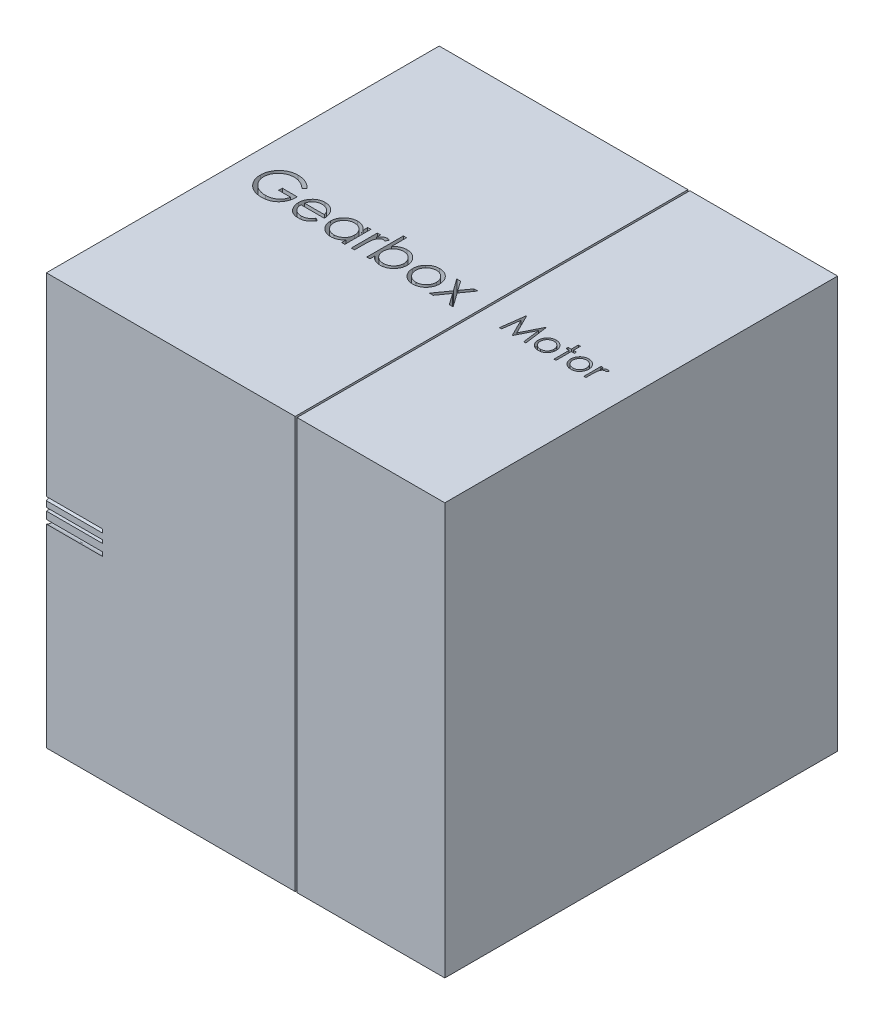
SolidWorks part; units mm, degrees
ref_plane "정면" through (0, 0, 0) normal (0, 0, 1) x (1, 0, 0)
ref_plane "윗면" through (0, 0, 0) normal (0, 1, 0) x (1, 0, 0)
ref_plane "우측면" through (0, 0, 0) normal (1, 0, 0) x (0, 0, -1)
sketch "Sketch1" plane through (0, 0, 0) normal (0, 1, 0) x (1, 0, 0)
  line L1 (106.5, -105) -> (-106.5, -105)
  line L2 (106.5, -105) -> (106.5, 105)
  line L3 (106.5, 105) -> (-106.5, 105)
  line L4 (-106.5, -105) -> (-106.5, 105)
  line L5 (106.5, -105) -> (-106.5, 105) construction
  line L6 (106.5, 105) -> (-106.5, -105) construction
  point P0 (0, 0)
  dimension "D1" = 210
  dimension "D2" = 213
extrude "Boss-Extrude1" add sketch "Sketch1" along normal blind 110 and the other way blind 110
sketch "Sketch2" plane through (0, 110, 0) normal (0, 1, 0) x (1, 0, 0)
  text T0 "Gearbox" font "Century Gothic" height in points 72
extrude "Cut-Extrude1" cut sketch "Sketch2" against normal blind 30
sketch "Sketch3" plane through (-106.5, 0, 0) normal (-1, 0, 0) x (0, 0, 1)
  text T0 "Wheel side\r\n" font "Century Gothic" height in points 72
extrude "Cut-Extrude2" cut sketch "Sketch3" against normal blind 30
sketch "Sketch4" plane through (0, 110, 0) normal (0, 1, 0) x (1, 0, 0)
  line L1 (106.5, 105) -> (-106.5, 105) construction
  line L2 (-106.5, -105) -> (106.5, -105) construction
  line L5 (26.5, 105) -> (27.5, 105)
  line L6 (26.5, 105) -> (26.5, -105)
  line L7 (26.5, -105) -> (27.5, -105)
  line L8 (27.5, 105) -> (27.5, -105)
  dimension "D1" = 1
extrude "Cut-Extrude3" cut sketch "Sketch4" against normal through all and the other way through all
sketch "Sketch5" plane through (0, 110, 0) normal (0, 1, 0) x (1, 0, 0)
  text T0 "Motor" font "Century Gothic" height in points 48
extrude "Cut-Extrude4" cut sketch "Sketch5" against normal blind 30
